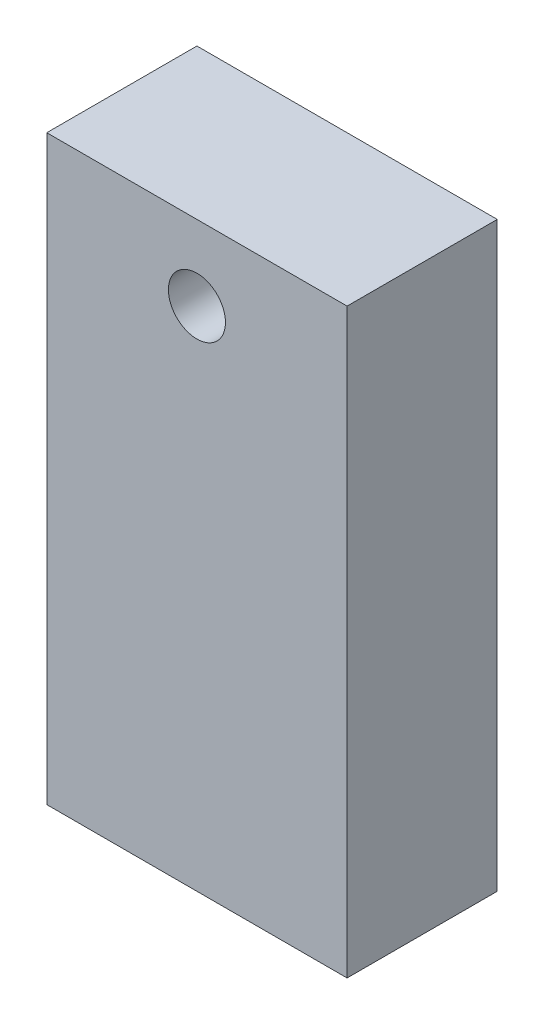
SolidWorks part; units mm, degrees
ref_plane "Front Plane" through (0, 0, 0) normal (0, 0, 1) x (1, 0, 0)
ref_plane "Top Plane" through (0, 0, 0) normal (0, 1, 0) x (1, 0, 0)
ref_plane "Right Plane" through (0, 0, 0) normal (1, 0, 0) x (0, 0, -1)
sketch "Sketch2" plane through (0, 0, 0) normal (0, 1, 0) x (1, 0, 0)
  line L1 (0, 0) -> (50.8, 0)
  line L2 (0, 0) -> (0, 25.4)
  line L3 (0, 25.4) -> (50.8, 25.4)
  line L4 (50.8, 0) -> (50.8, 25.4)
  dimension "D1" = 25.4
  dimension "D2" = 50.8
extrude "Boss-Extrude1" add sketch "Sketch2" along normal blind 98.425
sketch "Sketch3" plane through (0, 0, 0) normal (0, 0, 1) x (1, 0, 0)
  line L0 (0, 98.425) -> (50.8, 98.425) construction
  circle A0 centre (25.4, 85.725) radius 4.826
  dimension "D2" = 9.652
  dimension "D1" = 12.7
extrude "Cut-Extrude1" cut sketch "Sketch3" against normal through all
sketch "Sketch4" plane through (0, 0, 0) normal (0, -1, 0) x (-1, 0, 0)
  line L0 (0, 0) -> (-50.8, 0) construction
  line L1 (-25.4, 0) -> (-25.4, 8.3981)
  circle A0 centre (-12.7, 6.35) radius 2.667
  circle A1 centre (-38.1, 6.35) radius 2.667
  dimension "D2" = 5.334
  dimension "D3" = 5.334
  dimension "D4" = 25.4
  dimension "D1" = 6.35
  dimension "D5" = 12.7
extrude "Cut-Extrude2" cut sketch "Sketch4" against normal blind 19.05 contours A0 | A1 region at (12.7, 0, -6.35) region at (38.1, 0, -6.35)
